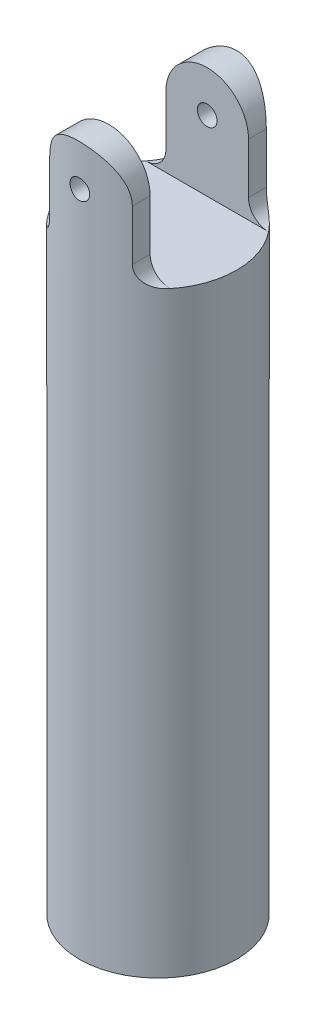
SolidWorks part; units mm, degrees
ref_plane "Front Plane" through (0, 0, 0) normal (0, 0, 1) x (1, 0, 0)
ref_plane "Top Plane" through (0, 0, 0) normal (0, 1, 0) x (1, 0, 0)
ref_plane "Right Plane" through (0, 0, 0) normal (1, 0, 0) x (0, 0, -1)
sketch "Sketch1" plane through (0, 0, 0) normal (0, 1, 0) x (1, 0, 0)
  circle A0 centre (0, 0) radius 6
  point P2 (0, 0)
  dimension "D1" = 12
extrude "Boss-Extrude1" add sketch "Sketch1" along normal blind 12
sketch "Sketch2" plane through (0, 0, 0) normal (1, 0, 0) x (0, 0, -1)
  line L0 (6, 12) -> (-6, 12) construction
  line L1 (-3.75, 12) -> (3.75, 12)
  line L2 (-3.75, 12) -> (-3.75, 3.5)
  line L3 (-3.75, 3.5) -> (3.75, 3.5)
  line L4 (3.75, 12) -> (3.75, 3.5)
  line L5 (-6, 0) -> (6, 0) construction
  point P8 (0, 3.5)
  point P9 (0, 0)
  dimension "D1" = 3.5
  dimension "D2" = 7.5
extrude "Cut-Extrude1" cut sketch "Sketch2" against normal through all both and the other way through all contours L2 L1 L4 L3
sketch "Sketch3" plane through (0, 0, 0) normal (0, 0, 1) x (1, 0, 0)
  line L0 (4.6837, 12) -> (-4.6837, 12) construction
  line L1 (-3.15, 8.85) -> (-3.15, 5)
  line L2 (-4.65, 3.5) -> (-4.6837, 3.5)
  line L3 (-4.6837, 12) -> (-4.6837, 3.5) construction
  line L4 (4.6837, 12) -> (-4.6837, 12)
  line L5 (-4.6837, 12) -> (-4.6837, 3.5)
  line L7 (0, -55) -> (0, 55) construction
  line L8 (4.6837, 12) -> (4.6837, 3.5)
  line L9 (4.65, 3.5) -> (4.6837, 3.5)
  line L10 (3.15, 8.85) -> (3.15, 5)
  arc A0 (3.15, 8.85) -> (-3.15, 8.85) centre (0, 8.85) ccw
  arc A1 (-3.15, 5) -> (-4.65, 3.5) centre (-4.65, 5) cw
  arc A2 (3.15, 5) -> (4.65, 3.5) centre (4.65, 5) ccw
  circle A3 centre (0, 8.85) radius 0.75
  dimension "D1" = 6.3
  dimension "D2" = 1.5
  dimension "D3" = 1.5
extrude "Cut-Extrude2" cut sketch "Sketch3" against normal through all both and the other way through all contours A1 L1 A0 L4 L5 L2 | L10 A2 L9 L8 L4 A0 | A3 region at (3.7178, 8.393, 0) region at (-3.7178, 8.393, 0) region at (0, 8.85, 0)
sketch "Sketch4" plane through (0, 0, 0) normal (0, -1, 0) x (1, 0, 0)
  line L1 (-0.6, 5) -> (0.6, 5)
  line L2 (-0.6, 5) -> (-0.6, 3.5)
  line L3 (-0.6, 3.5) -> (0.6, 3.5)
  line L4 (0.6, 5) -> (0.6, 3.5)
  line L5 (-0.6, 5) -> (0.6, 3.5) construction
  line L6 (-0.6, 3.5) -> (0.6, 5) construction
  line L7 (5, 1.15) -> (3.5, 1.15)
  line L8 (5, 1.15) -> (5, -1.15)
  line L9 (5, -1.15) -> (3.5, -1.15)
  line L10 (3.5, 1.15) -> (3.5, -1.15)
  line L11 (5, 1.15) -> (3.5, -1.15) construction
  line L12 (5, -1.15) -> (3.5, 1.15) construction
  line L13 (-5, -1.15) -> (-3.5, -1.15)
  line L14 (-5, -1.15) -> (-5, 1.15)
  line L15 (-5, 1.15) -> (-3.5, 1.15)
  line L16 (-3.5, -1.15) -> (-3.5, 1.15)
  line L17 (-5, -1.15) -> (-3.5, 1.15) construction
  line L18 (-5, 1.15) -> (-3.5, -1.15) construction
  line L19 (-0.6, -5) -> (0.6, -5)
  line L20 (-0.6, -5) -> (-0.6, -3.5)
  line L21 (-0.6, -3.5) -> (0.6, -3.5)
  line L22 (0.6, -5) -> (0.6, -3.5)
  line L23 (-0.6, -5) -> (0.6, -3.5) construction
  line L24 (-0.6, -3.5) -> (0.6, -5) construction
  circle A0 centre (0, 0) radius 4.25
  circle A1 centre (0, 0) radius 6 construction
  circle A2 centre (0, 0) radius 6
  point P3 (0, 4.25)
  point P8 (4.25, 0)
  point P13 (-4.25, 0)
  point P18 (0, -4.25)
  point P23 (0, 4.2186)
  point P24 (3.2207, 0.9086)
  point P25 (-0.6276, -3.5229)
  circle M26 centre (0, 0) radius 6
  dimension "D4" = 8.5
  dimension "D1" = 2.3
  dimension "D2" = 1.2
  dimension "D3" = 1.5
extrude "Boss-Extrude2" add sketch "Sketch4" along normal blind 42 contours A0 L22 L19 L20 L13 L14 L15 L2 L1 L4 L7 L8 L9 M26 region at (-5.8303, 0, 0)
